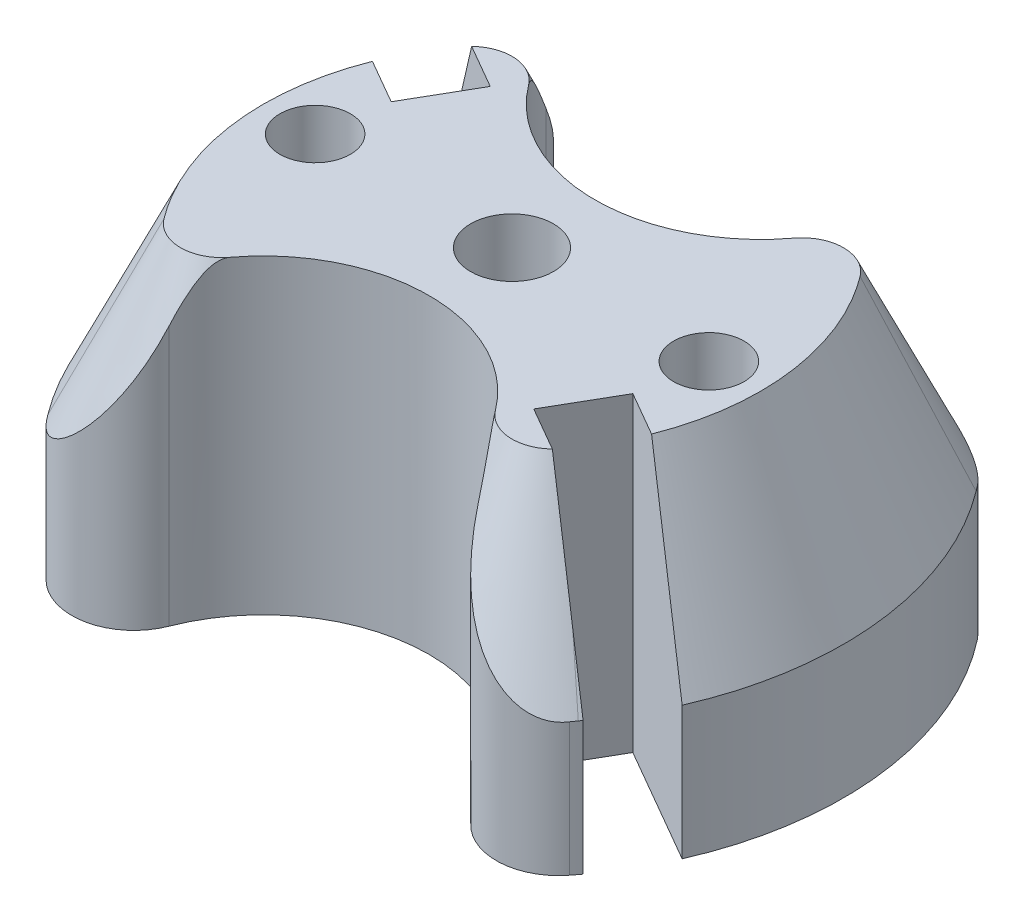
SolidWorks part; units mm, degrees
ref_plane "Front Plane" through (0, 0, 0) normal (0, 0, 1) x (1, 0, 0)
ref_plane "Top Plane" through (0, 0, 0) normal (0, 1, 0) x (1, 0, 0)
ref_plane "Right Plane" through (0, 0, 0) normal (1, 0, 0) x (0, 0, -1)
sketch "Sketch1" plane through (0, 0, 0) normal (0, 1, 0) x (1, 0, 0)
  line L0 (0, 0) -> (0, 14.7894) construction
  line L1 (0, 12) -> (0, -12) construction
  line L2 (-12, 0) -> (12, 0) construction
  circle A0 centre (-9.5, 0) radius 1.7
  circle A1 centre (9.5, 0) radius 1.7
  arc A2 (-6.4, 7.2) -> (6.4, 7.2) centre (0, 12) ccw
  arc A3 (-6.4, -7.2) -> (6.4, -7.2) centre (0, -12) cw
  arc A4 (-9.6, -7.2) -> (-6.4, -7.2) centre (-8, -6) ccw
  arc A5 (-6.4, 7.2) -> (-9.6, 7.2) centre (-8, 6) ccw
  arc A6 (9.6, 7.2) -> (6.4, 7.2) centre (8, 6) ccw
  arc A7 (6.4, -7.2) -> (9.6, -7.2) centre (8, -6) ccw
  ellipse E0 centre (0, 0) end of major axis (12, 0) minor radius 12 (-9.6, 7.2) -> (-9.6, -7.2) ccw
  ellipse E1 centre (0, 0) end of major axis (12, 0) minor radius 12 (9.6, -7.2) -> (9.6, 7.2) ccw
  dimension "D3" = 3.4
  dimension "D4" = 8
  dimension "D5" = 2
  dimension "D6" = 2
  dimension "D7" = 2
  dimension "D1" = 24
  dimension "D2" = 19
extrude "Boss-Extrude1" add sketch "Sketch1" against normal blind 15 draft 25 contours A1 | A0 | E0 A0 A1 region at (-9.5, 0, 0) region at (9.5, 0, 0) region at (0, 0, 0) draft outward yes
sketch "Sketch2" plane through (0, -15, 0) normal (0, -1, 0) x (1, 0, 0)
  circle A0 centre (0, 0) radius 2
  dimension "D1" = 4
extrude "Cut-Extrude1" cut sketch "Sketch2" against normal blind 17
sketch "Sketch3" plane through (0, 0, 0) normal (0, 1, 0) x (1, 0, 0)
  line L0 (0, 0) -> (5.569, -3.2153) construction
  line L1 (0, 0) -> (32.2896, 0) construction
  line L10 (7.2656, -6.2155) -> (9.0156, -3.1845)
  line L11 (7.2656, -6.2155) -> (24.5861, -16.2155)
  line L12 (9.0156, -3.1845) -> (26.3361, -13.1845)
  line L13 (24.5861, -16.2155) -> (26.3361, -13.1845)
  line L14 (0, 0) -> (-3.9347, -6.8151) construction
  line L15 (-26.3361, 13.1845) -> (-24.5861, 16.2155)
  line L16 (-7.2656, 6.2155) -> (-24.5861, 16.2155)
  line L17 (-9.0156, 3.1845) -> (-26.3361, 13.1845)
  line L18 (-9.0156, 3.1845) -> (-7.2656, 6.2155)
  arc A0 (-12.6116, 9.8462) -> (-12.6116, -9.8462) centre (0, 0) ccw
  circle A1 centre (0, 0) radius 32.0629
  arc A2 (-7.4523, 9.0909) -> (7.4523, 9.0909) centre (0, 12) ccw
  arc A4 (-7.4523, 9.0909) -> (-12.6116, 9.8462) centre (-10.247, 8) ccw
  arc A5 (7.4523, 9.0909) -> (12.6116, 9.8462) centre (10.247, 8) cw
  arc A6 (7.4523, -9.0909) -> (12.6116, -9.8462) centre (10.247, -8) ccw
  arc A7 (-7.4523, -9.0909) -> (7.4523, -9.0909) centre (0, -12) cw
  arc A8 (-7.4523, -9.0909) -> (-12.6116, -9.8462) centre (-10.247, -8) cw
  arc A9 (12.6116, -9.8462) -> (12.6116, 9.8462) centre (0, 0) ccw
  ellipse M35 centre (0, 0) end of major axis (0, 12) minor radius 12 (9.6, -7.2) -> (9.6, 7.2) ccw
  dimension "D1" = 30
  dimension "D5" = 32
  dimension "D6" = 3
  dimension "D7" = 3
  dimension "D2" = 3.5
  dimension "D3" = 9.4
  dimension "D4" = 20
extrude "Cut-Extrude2" cut sketch "Sketch3" against normal through all contours A1 A0 L12 L13 L11 L17 L15 L16 | A0 L16 L15 L17 | A0 L11 L13 L12 | L11 A0 L12 L10 | L11 A9 L12 M35 | L16 L15 L17 L18 region at (10.9847, 0, 6.342) region at (19.6449, 0, 11.342) region at (-19.6449, 0, -11.342) region at (-31.156, 0, 0)
extrude "Cut-Extrude3" cut sketch "Sketch1<3>" against normal blind 13 contours A1 | A0 region at (9.5, 0, 0)
sketch "Sketch1<3>" plane through (0, 0, 0) normal (0, 1, 0) x (1, 0, 0) same geometry as "Sketch1"
